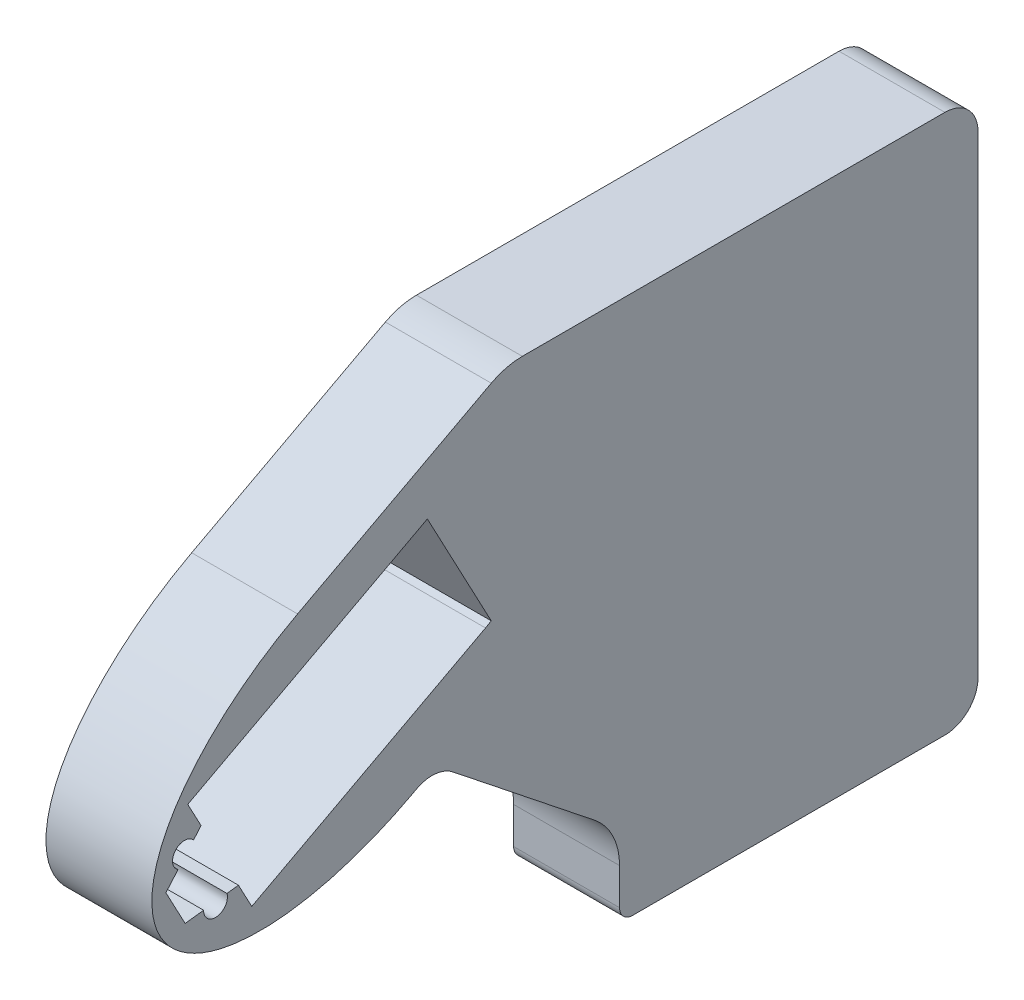
SolidWorks part; units mm, degrees
ref_plane "前视基准面" through (0, 0, 0) normal (0, 0, 1) x (1, 0, 0)
ref_plane "上视基准面" through (0, 0, 0) normal (0, 1, 0) x (1, 0, 0)
ref_plane "右视基准面" through (0, 0, 0) normal (1, 0, 0) x (0, 0, -1)
sketch "草图1" plane through (0, 0, 0) normal (1, 0, 0) x (0, 0, -1)
  line L0 (-6.1151, -25.0862) -> (-4.1019, -28.8725)
  line L3 (-3.7208, -40.1325) -> (-6.5056, -40.4731)
  line L5 (1.5428, -39.4887) -> (3.556, -43.275)
  line L8 (29.2028, -6.3074) -> (-6.1151, -25.0862)
  line L9 (38.8739, -24.4961) -> (3.556, -43.275)
  line L10 (59.1268, -65.7144) -> (59.1268, -71.2242)
  line L11 (10.4802, -8.461) -> (39.7427, 7.0982)
  line L16 (27.6629, -40.7768) -> (28.4593, -40.3534)
  line L17 (61.1268, -73.2242) -> (108.2851, -73.2242)
  line L18 (113.2851, -68.2242) -> (113.2851, 3.2687)
  line L19 (108.2851, 8.2687) -> (44.4374, 8.2687)
  line L21 (55.3485, -57.8856) -> (33.9175, -40.8537)
  line L22 (36.1073, -8.6401) -> (36.1063, -8.6406)
  line L23 (29.2028, -6.3074) -> (30.0858, -5.8379)
  line L25 (30.0858, -5.8379) -> (39.7427, -23.9999)
  line L26 (39.7427, -23.9999) -> (38.8739, -24.4961)
  line L29 (40.801, -17.472) -> (40.8018, -17.4716)
  line L39 (-6.5056, -40.4731) -> (-9.4186, -34.9945)
  line L40 (-4.1019, -28.8725) -> (-5.2452, -30.189)
  line L41 (1.5428, -39.4887) -> (-0.188, -39.7004)
  line L42 (-7.579, -32.8763) -> (-9.4186, -34.9945)
  circle A11 centre (40.801, -17.472) radius 1.8
  circle A12 centre (36.1073, -8.6401) radius 1.8
  arc A13 (-0.188, -39.7004) -> (-3.7208, -40.1325) centre (-1.9215, -40.1848) cw
  arc A14 (-5.2452, -30.189) -> (-7.579, -32.8763) centre (-6.6163, -31.3553) ccw
  arc A15 (55.3485, -57.8856) -> (59.1268, -65.7144) centre (49.1268, -65.7144) cw
  arc A16 (39.7427, 7.0982) -> (44.4374, 8.2687) centre (44.4374, -1.7313) cw
  arc A17 (108.2851, -73.2242) -> (113.2851, -68.2242) centre (108.2851, -68.2242) ccw
  arc A18 (113.2851, 3.2687) -> (108.2851, 8.2687) centre (108.2851, 3.2687) ccw
  arc A19 (33.9175, -40.8537) -> (28.4593, -40.3534) centre (30.8067, -44.7681) ccw
  arc A20 (59.1268, -71.2242) -> (61.1268, -73.2242) centre (61.1268, -71.2242) ccw
  ellipse E0 centre (19.0715, -24.6189) end of major axis (48.4513, -8.9974) minor radius 18.3 (10.4802, -8.461) -> (27.6629, -40.7768) ccw
  point P3 (34.0384, -15.4017)
  point P10 (6.3614, -10.4197)
  point P52 (-7.9621, -37.7338)
  point P54 (-4.2689, -35.7701)
  dimension "D1" = 10
  dimension "D2" = 5
  dimension "D3" = 5
  dimension "D4" = 2
extrude "凸台-拉伸1" add sketch "草图1" along normal blind 16 contours L18 A18 L19 A16 L11 E0 L16 A19 L21 A15 L10 A20 L17 A17
extrude "切除-拉伸3" cut sketch "草图1<12>" along normal blind 11 contours A11 | A14 | A13 | A12 region at (0, -17.472, -39.0519)
sketch "草图1<12>" plane through (0, 0, 0) normal (1, 0, 0) x (0, 0, -1) same geometry as "草图1"
sketch "草图3" plane through (0, 0, 0) normal (0, 1, 0) x (1, 0, 0)
  line L0 (0, 113.2851) -> (16, 113.2851)
  line L3 (0, 113.2851) -> (-10.0484, 113.2851)
  line L9 (8, 113.2851) -> (-10.0484, 113.2851)
  line L10 (30, 97.764) -> (30, 97.4499)
  line L11 (30, 97.764) -> (30, 97.4499)
  circle A12 centre (9.9612, 103.4793) radius 1.6
  circle A13 centre (9.9993, 93.4793) radius 1.6
  circle A14 centre (10, 83.4793) radius 1.6
  circle A15 centre (10, 73.4793) radius 1.6
  circle A16 centre (10, 65.4793) radius 1.6
  dimension "D1" = 10
  dimension "D5" = 10
  dimension "D6" = 10
  dimension "D2" = 10
  dimension "D7" = 8
extrude "切除-拉伸5" cut sketch "草图3" against normal through all both and the other way through all contours A12 | A13 | A14 | A15 | A16
sketch "草图5" plane through (0, 0, 0) normal (0, 1, 0) x (1, 0, 0)
  line L0 (3.9558, 107.8663) -> (15.1043, 107.8663)
  line L1 (15.1043, 107.8663) -> (15.1043, 61.43)
  line L2 (15.1043, 61.43) -> (3.9558, 61.43)
  line L3 (3.9558, 61.43) -> (3.9558, 107.8663)
  point P2 (0, 0)
  point P5 (15.1043, 61.43)
extrude "凸台-拉伸5" add sketch "草图5" along normal through all contours L3 L0 L1 L2
extrude "切除-拉伸7" cut sketch "草图1<19>" along normal blind 20 contours L25 L26 L9 L5 L41 A13 L3 L39 L42 A14 L40 L0 L8 L23
sketch "草图1<19>" plane through (0, 0, 0) normal (1, 0, 0) x (0, 0, -1) same geometry as "草图1"
